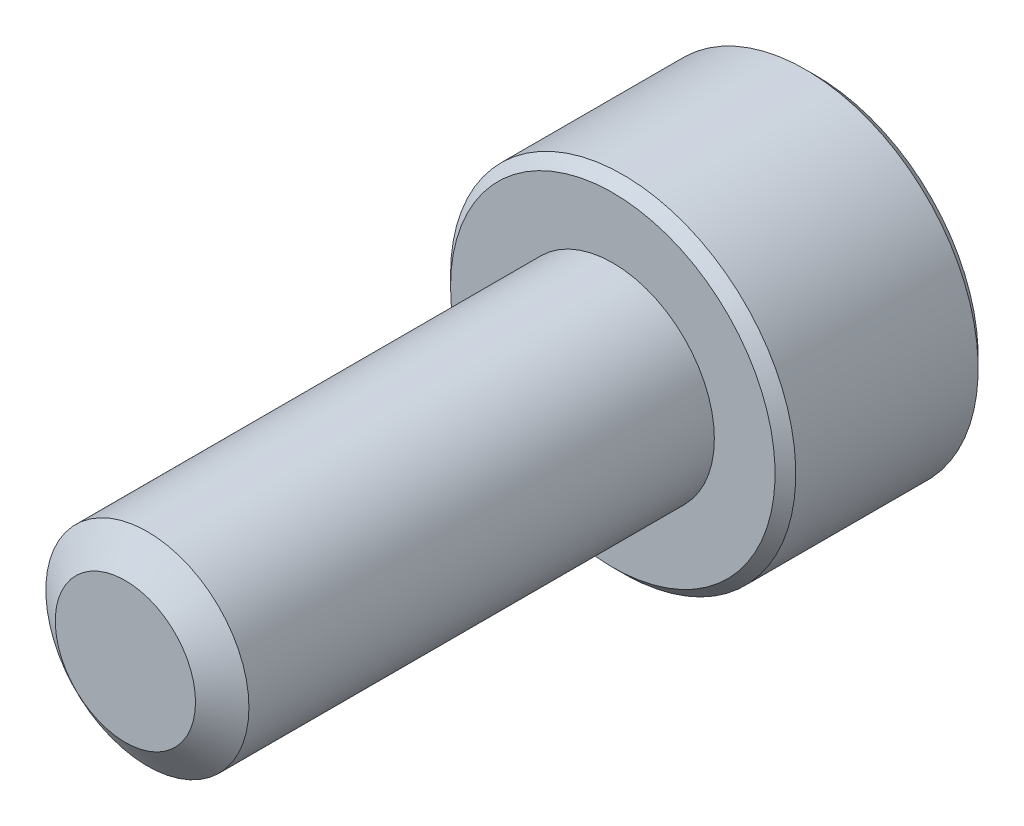
SolidWorks part; units mm, degrees
ref_plane "Front Plane" through (0, 0, 0) normal (0, 0, 1) x (1, 0, 0)
ref_plane "Top Plane" through (0, 0, 0) normal (0, 1, 0) x (1, 0, 0)
ref_plane "Right Plane" through (0, 0, 0) normal (1, 0, 0) x (0, 0, -1)
sketch "Sketch1" plane through (0, 0, 0) normal (0, 0, 1) x (1, 0, 0)
  circle A0 centre (0, 0) radius 2.5
  dimension "OD" = 5
extrude "Extrude1" add sketch "Sketch1" against normal blind 12
sketch "Sketch2" plane through (0, 0, 0) normal (0, 0, 1) x (1, 0, 0)
  circle A0 centre (0, 0) radius 2.5 construction
  circle A1 centre (0, 0) radius 2.5
curve "Helix/Spiral1" pitch 0.8 height 12.8 turns 16 parameters "pitch"=0.8
sketch "Sketch3" plane through (0, 0, 0) normal (1, 0, 0) x (0, 0, -1)
  line L0 (-0.7, 2.5) -> (-0.4, 1.9804)
  line L1 (-0.4, 1.9804) -> (-0.3, 1.9804)
  line L2 (-0.3, 1.9804) -> (0, 2.5)
  line L3 (-0.7, 2.5) -> (0, 2.5)
  line L4 (-0.35, 2.5) -> (-0.35, 1.9804) construction
  line L5 (-0.55, 2.2402) -> (-0.15, 2.2402) construction
  line L6 (0, 2.5) -> (0, -2.5) construction
  line L7 (0, -2.5) -> (12, -2.5) construction
  point P11 (3.6, -2.5)
  dimension "D1" = 0.1
  dimension "D2" = 0.4
  dimension "D3" = 60
  dimension "D4" = 3.6
sweep "Cut-Sweep1" [suppressed] cut profiles "Sketch3" path "Helix/Spiral1"
sketch "Sketch4" plane through (0, 0, 0) normal (1, 0, 0) x (0, 0, -1)
  line L0 (0.5417, 2.5) -> (0, 1.7264)
  line L1 (0, 1.7264) -> (0, 2.5)
  line L2 (0.5417, 2.5) -> (0, 2.5)
  line L3 (-0.7, 2.5) -> (0, 2.5) construction
  line L4 (0, 0) -> (7.0209, 0) construction
  dimension "D1" = 55
  dimension "D2" = 0.254
revolve "Cut-Revolve1" cut sketch "Sketch4" angle 360 about L4
sketch "Sketch5" [suppressed] plane through (0, 0, 0) normal (1, 0, 0) x (0, 0, -1)
  line L0 (12, -1.991) -> (12, 1.7838) construction
  line L1 (12, 2.5) -> (0.1203, 2.5)
  line L2 (12, 2.5) -> (12, 0)
  line L3 (12, 0) -> (0.0001, 0)
  line L4 (0.0001, 2.1698) -> (0.0001, 0)
  line L5 (0.1203, 2.5) -> (0.0001, 2.1698)
  line L6 (0, 0) -> (9.9695, 0) construction
  point P3 (0.0001, 2.5)
  point P10 (0.0001, 2.5)
  dimension "D1" = 0.3302
  dimension "Thread min" = 0.0001
  dimension "D3" = 20
revolve "partially thread" [suppressed] add sketch "Sketch5" angle 360 about L6
sketch "Sketch6" plane through (0, 0, -12) normal (0, 0, -1) x (-1, 0, 0)
  circle A0 centre (0, 0) radius 4.25
  dimension "head dia" = 8.5
extrude "Extrude2" add sketch "Sketch6" along normal blind 5
sketch "Sketch7" plane through (0, 0, -17) normal (0, 0, -1) x (-1, 0, 0)
  line L1 (0, 2.3094) -> (-2, 1.1547)
  line L2 (-2, 1.1547) -> (-2, -1.1547)
  line L3 (-2, -1.1547) -> (0, -2.3094)
  line L4 (0, -2.3094) -> (2, -1.1547)
  line L5 (2, -1.1547) -> (2, 1.1547)
  line L6 (2, 1.1547) -> (0, 2.3094)
  circle A0 centre (0, 0) radius 2 construction
  dimension "hex dia" = 4
extrude "Cut-Extrude1" cut sketch "Sketch7" against normal blind 3
sketch "Sketch8" plane through (0, 0, -17) normal (0, 0, -1) x (-1, 0, 0)
  circle A0 centre (0, 0) radius 2.3094
extrude "Cut-Extrude2" cut sketch "Sketch8" against normal through all draft 45
chamfer "Chamfer1" distance 0.255 angle 45 2 edges at (-4.25, 0, -17) (-4.25, 0, -12)
sketch "Sketch9" plane through (0, 0, 0) normal (1, 0, 0) x (0, 0, -1)
  line L0 (0, 2.5) -> (0, -2.5) construction
  line L1 (4.4, 2.5) -> (4.4, -2.5) construction
  dimension "D1" = 4.4
sketch "Sketch10" plane through (0, 0, 0) normal (1, 0, 0) x (0, 0, -1)
  line L0 (12, 2.5) -> (12, 0)
  line L1 (12, 2.5) -> (11.8, 2.5)
  line L2 (11.8, 2.5) -> (10.7645, 0)
  line L3 (12, 0) -> (10.7645, 0)
  line L4 (12, 3.995) -> (12, -3.995) construction
  dimension "D1" = 22.5
  dimension "D2" = 0.2
revolve "Revolve1" add sketch "Sketch10" angle 360 about L3
equation "\"D3@Helix/Spiral1\" = \"screw length@Extrude1\"+\"pitch@Helix/Spiral1\""
equation "\"D1@Sketch3\" = \"pitch@Helix/Spiral1\"*.125"
equation "\"D2@Sketch3\" = \"pitch@Helix/Spiral1\"*.5"
equation "\"D1@Cut-Extrude1\" = \"hex dia@Sketch7\"*.75"
equation "\"D1@Chamfer1\" = \"head dia@Sketch6\"*.03"
equation "\"D1@Sketch9\" = \"pitch@Helix/Spiral1\"*5.5"
equation "\"D2@Sketch10\" = \"pitch@Helix/Spiral1\"*.25"
equation "\"D4@Sketch3\" = \"pitch@Helix/Spiral1\"*4.50"
